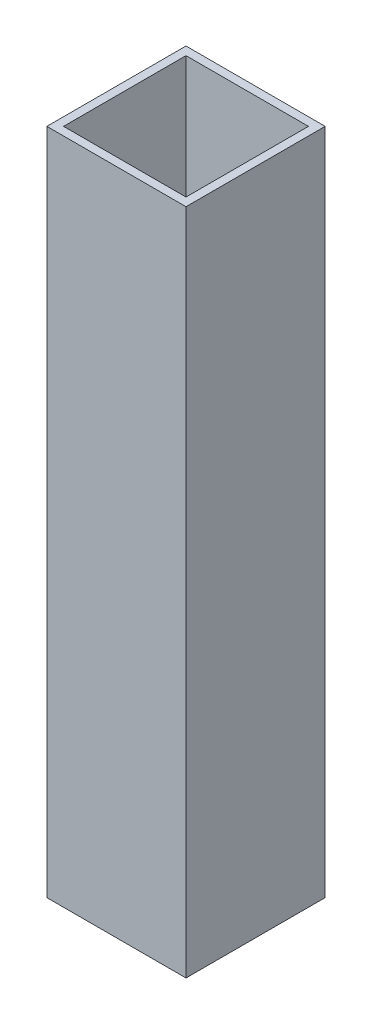
SolidWorks part; units mm, degrees
material "1060 Alloy"
ref_plane "Front Plane" through (0, 0, 0) normal (0, 0, 1) x (1, 0, 0)
ref_plane "Top Plane" through (0, 0, 0) normal (0, 1, 0) x (1, 0, 0)
ref_plane "Right Plane" through (0, 0, 0) normal (1, 0, 0) x (0, 0, -1)
sketch "Sketch1" plane through (0, 0, 0) normal (0, 1, 0) x (1, 0, 0)
  line L0 (0, 63.6278) -> (0, -69.3975) construction
  line L1 (-105.4586, 0) -> (105.4586, 0) construction
  line L2 (-11, 11) -> (-11, -11)
  line L3 (-12.5, 12.5) -> (12.5, 12.5)
  line L4 (-12.5, 12.5) -> (-12.5, -12.5)
  line L5 (-12.5, -12.5) -> (12.5, -12.5)
  line L6 (12.5, 12.5) -> (12.5, -12.5)
  line L7 (-11, -11) -> (11, -11)
  line L8 (11, 11) -> (11, -11)
  line L13 (-11, 11) -> (11, 11)
  point P5 (0, 0)
  dimension "D1" = 25
  dimension "D2" = 25
  dimension "D3" = 0
  dimension "D4" = 1.5
  dimension "D5" = 11
  dimension "D6" = 11
extrude "Boss-Extrude1" add sketch "Sketch1" along normal blind 60 and the other way blind 60
